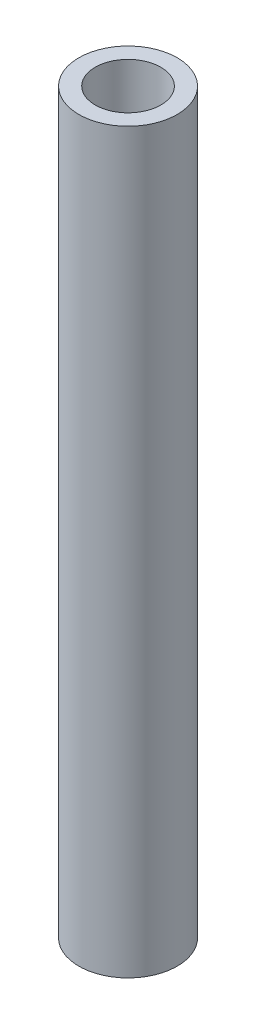
SolidWorks part; units mm, degrees
ref_plane "Front Plane" through (0, 0, 0) normal (0, 0, 1) x (1, 0, 0)
ref_plane "Top Plane" through (0, 0, 0) normal (0, 1, 0) x (1, 0, 0)
ref_plane "Right Plane" through (0, 0, 0) normal (1, 0, 0) x (0, 0, -1)
sketch "Sketch1" plane through (0, 0, 0) normal (1, 0, 0) x (0, 0, -1)
  line L0 (0, 0) -> (0, -450)
  dimension "D1" = 450
sweep "Sweep-Thin2" add path "Sketch1" circular profile diameter 60 parameters "D1"=10, "D3"=60
